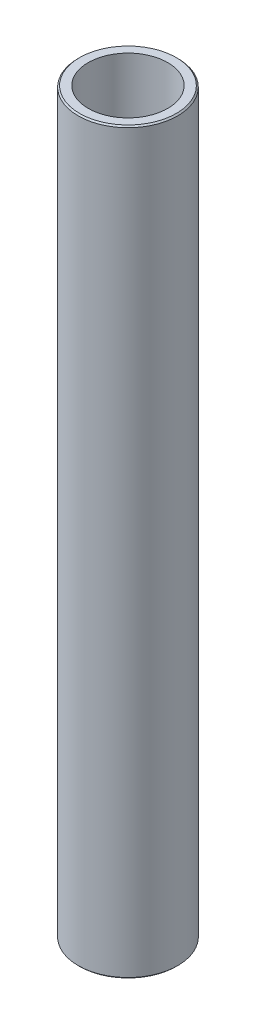
SolidWorks part; units mm, degrees
ref_plane "Front Plane" through (0, 0, 0) normal (0, 0, 1) x (1, 0, 0)
ref_plane "Top Plane" through (0, 0, 0) normal (0, 1, 0) x (1, 0, 0)
ref_plane "Right Plane" through (0, 0, 0) normal (1, 0, 0) x (0, 0, -1)
sketch "Sketch1" plane through (0, 0, 0) normal (0, 1, 0) x (1, 0, 0)
  circle A0 centre (0, 0) radius 40
  dimension "SHAFT_OD" = 80
extrude "Boss-Extrude1" add sketch "Sketch1" along normal blind 593.671
sketch "Sketch2" plane through (0, 0, 0) normal (0, 1, 0) x (1, 0, 0)
  circle A0 centre (0, 0) radius 31.9476
  dimension "BORE_D" = 63.8951
extrude "Cut-Extrude1" cut sketch "Sketch2" along normal through all
chamfer "Chamfer1" distance 1.1163 angle 45 2 edges at (0, 593.671, 40) (0, 0, 40)
